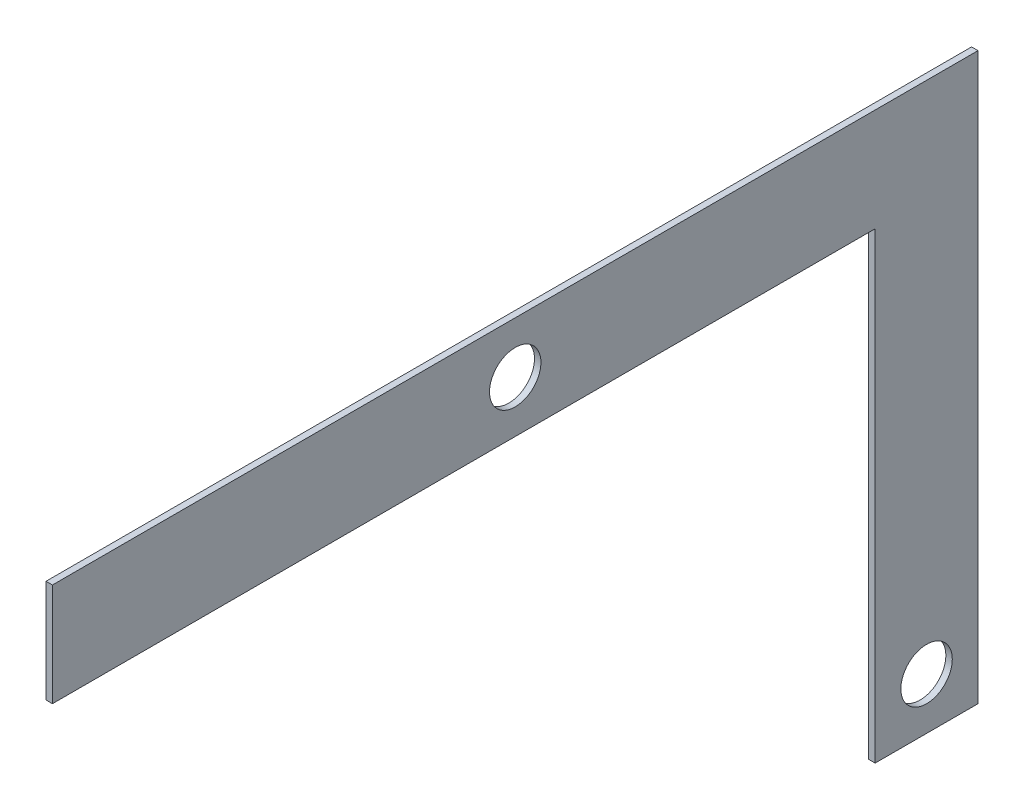
SolidWorks part; units mm, degrees
material "6063-O"
ref_plane "Front" through (0, 0, 0) normal (0, 0, 1) x (1, 0, 0)
ref_plane "Top" through (0, 0, 0) normal (0, 1, 0) x (1, 0, 0)
ref_plane "Right" through (0, 0, 0) normal (1, 0, 0) x (0, 0, -1)
sketch "Sketch1" plane through (0, 0, 0) normal (1, 0, 0) x (0, 0, -1)
  line L0 (0, 25.4) -> (0, -25.4) construction
  line L1 (-228.6, 25.4) -> (228.6, 25.4)
  line L2 (-228.6, 25.4) -> (-228.6, -254)
  line L3 (-177.8, -25.4) -> (177.8, -25.4)
  line L4 (228.6, 25.4) -> (228.6, -254)
  line L7 (228.6, -254) -> (177.8, -254)
  line L8 (177.8, -25.4) -> (177.8, -254)
  line L11 (-228.6, -254) -> (-177.8, -254)
  line L12 (-177.8, -25.4) -> (-177.8, -254)
  circle A0 centre (0, 0) radius 12.7
  point P12 (0, 0)
  dimension "D5" = 25.4
  dimension "D1" = 50.8
  dimension "D2" = 50.8
  dimension "D3" = 457.2
  dimension "D4" = 228.6
extrude "Boss-Extrude1" add sketch "Sketch1" along normal blind 3.175
sketch "Sketch3" plane through (3.175, 0, 0) normal (1, 0, 0) x (0, 0, -1)
  line L0 (-279.2989, -228.6) -> (49720.7011, -228.6) construction
  line L1 (-228.6, -254) -> (-177.8, -254) construction
  line L2 (-203.2, -254) -> (-203.2, 25.4) construction
  line L3 (228.6, 25.4) -> (-228.6, 25.4) construction
  line L4 (203.2, -254) -> (203.2, 25.4) construction
  line L5 (177.8, -254) -> (228.6, -254) construction
  circle A0 centre (-203.2, -228.6) radius 12.7
  circle A1 centre (203.2, -228.6) radius 12.7
  point P12 (-203.2, -228.6)
  point P13 (203.2, -228.6)
  dimension "D2" = 25.4
  dimension "D1" = 25.4
extrude "Cut-Extrude1" cut sketch "Sketch3" against normal through all
sketch "Sketch4" plane through (3.175, 0, 0) normal (1, 0, 0) x (0, 0, -1)
  line L1 (-177.8, -25.4) -> (-228.6, -25.4)
  line L2 (-177.8, -25.4) -> (-177.8, -254)
  line L3 (-177.8, -254) -> (-228.6, -254)
  line L4 (-228.6, -25.4) -> (-228.6, -254)
extrude "Cut-Extrude2" cut sketch "Sketch4" against normal through all
